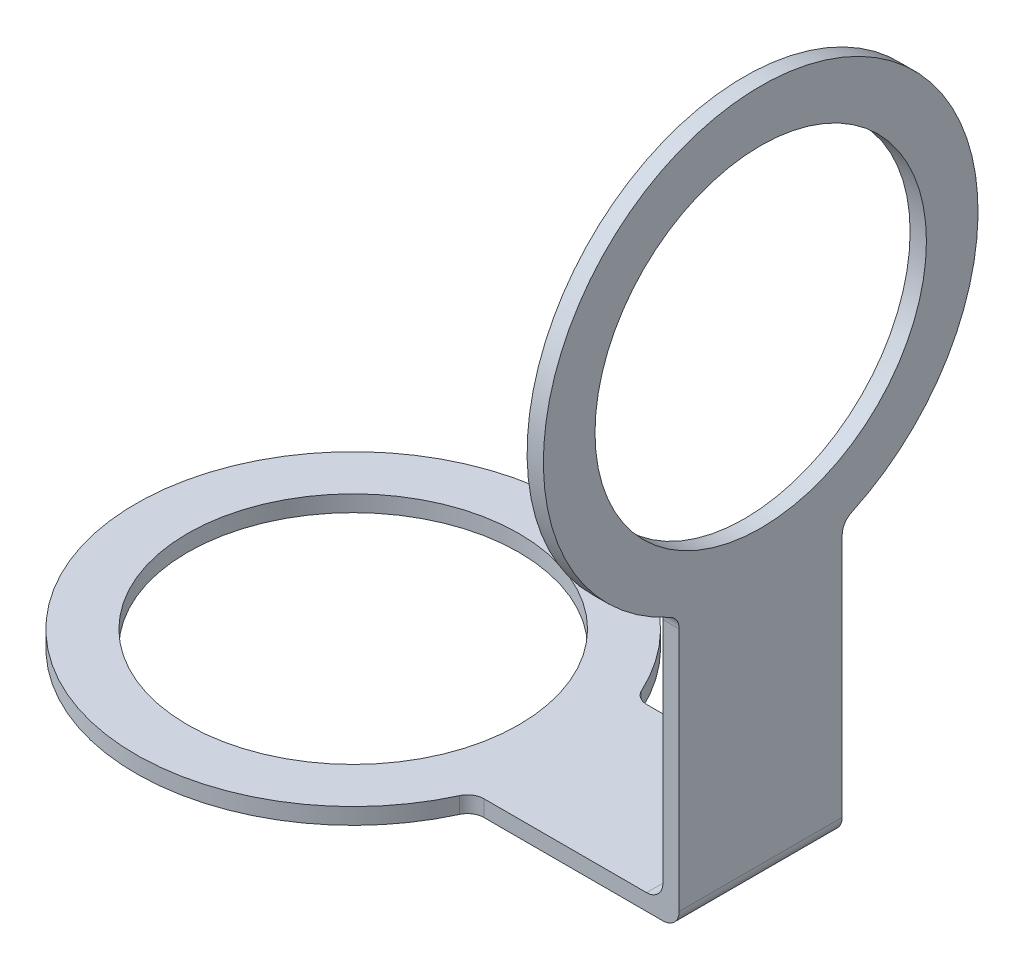
SolidWorks part; units mm, degrees
ref_plane "Front Plane" through (0, 0, 0) normal (0, 0, 1) x (1, 0, 0)
ref_plane "Top Plane" through (0, 0, 0) normal (0, 1, 0) x (1, 0, 0)
ref_plane "Right Plane" through (0, 0, 0) normal (1, 0, 0) x (0, 0, -1)
sketch "Sketch1" plane through (0, 0, 0) normal (0, 1, 0) x (1, 0, 0)
  circle A0 centre (0, 0) radius 40
  circle A1 centre (0, 0) radius 30.5
  dimension "D1" = 80
  dimension "D2" = 61
extrude "Boss-Extrude1" add sketch "Sketch1" along normal blind 3
sketch "Sketch2" plane through (0, 3, 0) normal (0, 1, 0) x (1, 0, 0)
  line L1 (35, 15) -> (75, 15)
  line L2 (35, 15) -> (35, -15)
  line L3 (35, -15) -> (75, -15)
  line L4 (75, 15) -> (75, -15)
  circle A0 centre (0, 0) radius 30.5 construction
  dimension "D1" = 30
  dimension "D2" = 15
  dimension "D3" = 35
  dimension "D4" = 40
extrude "Boss-Extrude2" add sketch "Sketch2" against normal up to surface (3 mm away) up to face at (0, 0, 40)
sketch "Sketch3" plane through (75, 0, 0) normal (1, 0, 0) x (0, 0, -1)
  line L0 (15, 0) -> (15, 3) construction
  line L1 (-15, 0) -> (15, 0)
  line L2 (-15, 0) -> (-15, 50)
  line L4 (15, 0) -> (15, 50)
  arc A0 (15, 50) -> (-15, 50) centre (0, 87.081) ccw
  circle A1 centre (0, 87.081) radius 30.5
  point P8 (0, 0)
  point P10 (0, 0)
  point P11 (0, 0)
  dimension "D1" = 80
  dimension "D2" = 61
  dimension "D3" = 50
extrude "Boss-Extrude3" add sketch "Sketch3" against normal blind 3
fillet "Fillet1" radius 3 4 edges at (37.081, 1.5, 15) (37.081, 1.5, -15) (73.5, 50, 15) (73.5, 50, -15)
fillet "Fillet2" radius 3 2 edges at (72, 3, 0) (75, 0, 0)
